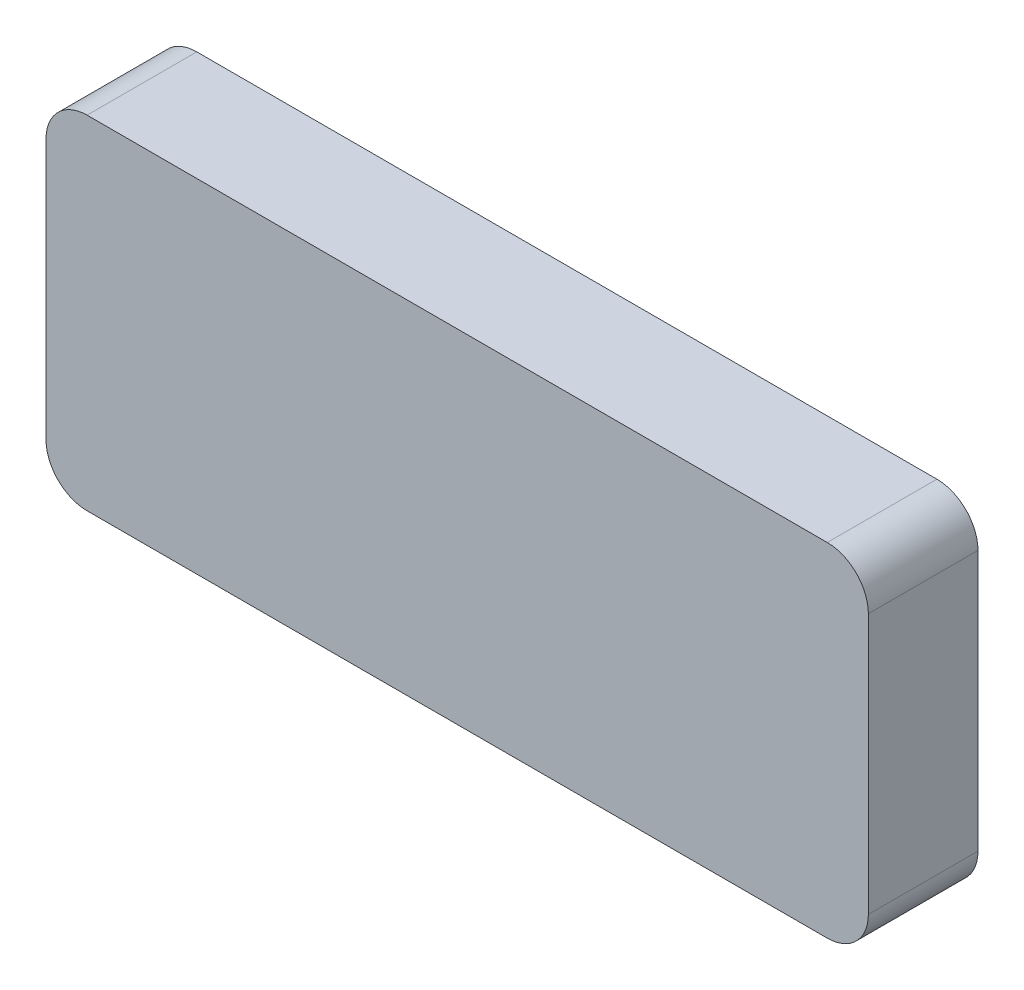
SolidWorks part; units mm, degrees
ref_plane "Ön Düzlem" through (0, 0, 0) normal (0, 0, 1) x (1, 0, 0)
ref_plane "Üst Düzlem" through (0, 0, 0) normal (0, 1, 0) x (1, 0, 0)
ref_plane "Sağ Düzlem" through (0, 0, 0) normal (1, 0, 0) x (0, 0, -1)
sketch "Çizim1" plane through (0, 0, 0) normal (0, 0, 1) x (1, 0, 0)
  line L1 (-30, 12.5) -> (30, 12.5)
  line L2 (-30, 12.5) -> (-30, -12.5)
  line L3 (-30, -12.5) -> (30, -12.5)
  line L4 (30, 12.5) -> (30, -12.5)
  line L5 (-30, 12.5) -> (30, -12.5) construction
  line L6 (-30, -12.5) -> (30, 12.5) construction
  point P0 (0, 0)
  dimension "D1" = 60
  dimension "D2" = 25
base flange "Taban-Flanş1" sketch "Çizim1" thickness 8 reverse thickness direction no parameters "D1"=4
fillet "Radyus1" radius 3 4 edges at (30, 12.5, -4) (30, -12.5, -4) (-30, -12.5, -4) (-30, 12.5, -4)
sketch "Büküm-Çizgileri1" [suppressed] plane through (0, 0, 0) normal (0, 1, 0) x (1, 0, 0)
sketch "Sınırlandırma-Kutusu1" [suppressed] plane through (0, 0, 0) normal (0, 1, 0) x (1, 0, 0)
sheet metal parameters "Sac-Levha1" thickness 8 parameters "D1"=4
flat pattern "Düz-Çoğaltma1" [suppressed]
sketch "Büküm-Çizgileri2" plane through (0, 0, 0) normal (0, 1, 0) x (1, 0, 0)
sketch3d "Sınırlandırma-Kutusu2" [suppressed]
  line L0 (-30, 12.5, 0) -> (30, 12.5, 0) construction
  line L1 (-30, -12.5, 0) -> (30, -12.5, 0) construction
  line L2 (-30, 12.5, 0) -> (-30, -12.5, 0) construction
  line L3 (30, 12.5, 0) -> (30, -12.5, 0) construction
